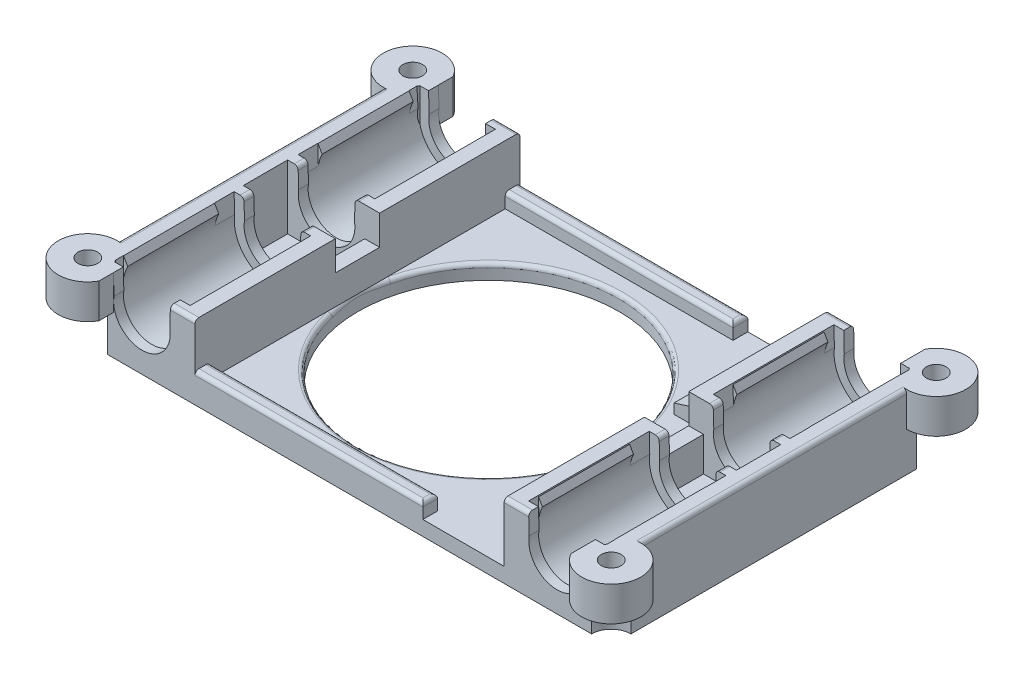
SolidWorks part; units mm, degrees
ref_plane "Front" through (0, 0, 0) normal (0, 0, 1) x (1, 0, 0)
ref_plane "Top" through (0, 0, 0) normal (0, 1, 0) x (1, 0, 0)
ref_plane "Right" through (0, 0, 0) normal (1, 0, 0) x (0, 0, -1)
sketch "Sketch1" plane through (0, 0, 0) normal (0, 1, 0) x (1, 0, 0)
  line L1 (-62.38, 33) -> (62.38, 33)
  line L2 (-62.38, 33) -> (-62.38, -33)
  line L3 (-62.38, -33) -> (62.38, -33)
  line L4 (62.38, 33) -> (62.38, -33)
  dimension "D1" = 124.76
  dimension "D2" = 66
  dimension "6" = 62.38
  dimension "D4" = 33
extrude "Boss-Extrude1" add sketch "Sketch1" along normal blind 20
sketch "Sketch2" plane through (0, 0, 33) normal (0, 0, 1) x (1, 0, 0)
  line L0 (-62.38, 0) -> (62.38, 0) construction
  line L1 (-62.38, 20) -> (-62.38, 0) construction
  line L2 (62.38, 20) -> (62.38, 0) construction
  circle A0 centre (-42.16, 10) radius 7.75
  circle A1 centre (42.16, 10) radius 7.65
  dimension "D2" = 15.5
  dimension "D3" = 15.3
  dimension "D1" = 20.22
  dimension "D4" = 10
  dimension "D5" = 10
  dimension "D6" = 20.22
  dimension "D7" = 84.32
extrude "Cut-Extrude1" cut sketch "Sketch2" against normal through all
sketch "Sketch4" plane through (-62.38, 0, 0) normal (-1, 0, 0) x (0, 0, 1)
  line L0 (-33, 20) -> (33, 20) construction
  line L1 (31, 2) -> (-31, 2)
  line L2 (31, 2) -> (31, 20)
  line L3 (31, 20) -> (-31, 20)
  line L4 (-31, 2) -> (-31, 20)
  line L5 (-33, 0) -> (33, 0) construction
  line L6 (33, 2.35) -> (33, 17.65) construction
  line L9 (-33, 20) -> (-33, 0) construction
  dimension "D1" = 2
  dimension "D2" = 2
  dimension "D3" = 2
extrude "Cut-Extrude2" cut sketch "Sketch4" against normal blind 27.98
sketch "Sketch5" plane through (62.38, 0, 0) normal (1, 0, 0) x (0, 0, -1)
  line L0 (-33, 20) -> (33, 20) construction
  line L1 (-31, 2) -> (31, 2)
  line L2 (-31, 2) -> (-31, 20)
  line L3 (-31, 20) -> (31, 20)
  line L4 (31, 2) -> (31, 20)
  line L5 (-33, 0) -> (33, 0) construction
  line L6 (-33, 20) -> (-33, 0) construction
  line L7 (33, 20) -> (33, 0) construction
  dimension "D1" = 2
  dimension "D2" = 2
  dimension "D3" = 2
extrude "Cut-Extrude3" cut sketch "Sketch5" against normal blind 27.98
sketch "Sketch6" plane through (0, 0, 31) normal (0, 0, -1) x (-1, 0, 0)
  line L0 (34.4, 20) -> (62.38, 20) construction
  line L1 (31.16, 20) -> (53.16, 20)
  line L2 (31.16, 20) -> (31.16, 2)
  line L3 (31.16, 2) -> (53.16, 2)
  line L4 (53.16, 20) -> (53.16, 2)
  line L5 (34.4, 2) -> (62.38, 2) construction
  circle A0 centre (42.16, 10) radius 7.75 construction
  circle A1 centre (42.16, 10) radius 7.75
  dimension "D1" = 22
  dimension "D2" = 11
extrude "Boss-Extrude2" add sketch "Sketch6" along normal blind 24.5
mirror "Mirror1" about plane through (0, 0, 0) normal (0, 0, 1) of "Boss-Extrude2"
mirror "Mirror2" about plane through (0, 0, 0) normal (1, 0, 0) of "Mirror1", "Boss-Extrude2"
sketch "Sketch7" plane through (0, 0, 33) normal (0, 0, 1) x (1, 0, 0)
  line L0 (34.5126, 9.8) -> (34.2459, 20)
  line L2 (-62.38, 20) -> (62.38, 20) construction
  line L3 (34.2459, 20) -> (50.0741, 20)
  line L4 (50.0741, 20) -> (49.8074, 9.8)
  circle A1 centre (42.16, 10) radius 7.65 construction
  arc A2 (34.5126, 9.8) -> (49.8074, 9.8) centre (42.16, 10) ccw
  dimension "D1" = 0.2
  dimension "D2" = 0.2
extrude "Cut-Extrude4" cut sketch "Sketch7" against normal blind 4
mirror "Mirror3" about plane through (0, 0, 0) normal (1, 0, 0) of "Cut-Extrude4"
mirror "Mirror4" about plane through (0, 0, 0) normal (0, 0, 1) of "Mirror3", "Cut-Extrude4"
sketch "Sketch8" plane through (0, 0, -6.5) normal (0, 0, 1) x (1, 0, 0)
  line L0 (49.8074, 9.8) -> (50.0741, 20) construction
  line L1 (34.2459, 20) -> (34.5126, 9.8) construction
  line L2 (49.8074, 9.8) -> (50.0741, 20)
  line L3 (34.2459, 20) -> (34.5126, 9.8)
  line L4 (50.0741, 20) -> (34.2459, 20)
  arc A0 (34.5126, 9.8) -> (49.8074, 9.8) centre (42.16, 10) ccw construction
  arc A1 (34.5126, 9.8) -> (49.8074, 9.8) centre (42.16, 10) ccw
extrude "Cut-Extrude5" cut sketch "Sketch8" against normal blind 4
mirror "Mirror5" about plane through (0, 0, 0) normal (1, 0, 0) of "Cut-Extrude5"
mirror "Mirror6" about plane through (0, 0, 0) normal (0, 0, 1) of "Mirror5", "Cut-Extrude5"
sketch "Sketch10" plane through (0, 0, -29) normal (0, 0, -1) x (-1, 0, 0)
  line L0 (34.3838, 14.7273) -> (35.1748, 13.3571)
  line L1 (49.8398, 11.0405) -> (50.0741, 20) construction
  line L2 (49.9454, 15.0786) -> (50.0741, 20)
  line L3 (50.0741, 20) -> (34.2459, 20)
  line L4 (34.2459, 20) -> (34.3838, 14.7273)
  line L5 (34.2459, 20) -> (34.4802, 11.0405) construction
  line L7 (49.0556, 13.5374) -> (49.9454, 15.0786)
  arc A0 (49.8398, 11.0405) -> (34.4802, 11.0405) centre (42.16, 10) ccw construction
  arc A1 (49.0556, 13.5374) -> (35.1748, 13.3571) centre (42.16, 10) ccw
  point P11 (0, 0)
  dimension "D2" = 151.498
  dimension "D1" = 151.498
extrude "Cut-Extrude6" cut sketch "Sketch10" against normal through all both and the other way through all
mirror "Mirror7" about plane through (0, 0, 0) normal (1, 0, 0) of "Cut-Extrude6"
ref_plane "Plane6" through (0, 10, 0) normal (0, 1, 0) x (1, 0, 0)
sketch "Sketch12" plane through (0, 0, -33) normal (0, 0, -1) x (-1, 0, 0)
  line L2 (48.0748, 20.0523) -> (62.38, 20)
  line L3 (62.38, 20) -> (62.38, 0)
  line L4 (36.2452, 20.0523) -> (36.484, 10.9196)
  line L5 (47.836, 10.9196) -> (48.0748, 20.0523)
  line L6 (36.2452, 20.0523) -> (36.484, 10.9196)
  line L7 (47.836, 10.9196) -> (48.0748, 20.0523)
  line L8 (62.38, 0) -> (30.8026, 0)
  line L9 (-62.38, 0) -> (62.38, 0) construction
  line L10 (30.8026, 0) -> (30.8026, 20)
  line L11 (-34.2459, 20) -> (34.2459, 20) construction
  line L12 (30.8026, 20) -> (36.2452, 20.0523)
  arc A2 (36.484, 10.9196) -> (47.836, 10.9196) centre (42.16, 10) ccw
  arc A3 (36.484, 10.9196) -> (47.836, 10.9196) centre (42.16, 10) ccw
  dimension "D1" = 2
extrude "Boss-Extrude3" add sketch "Sketch12" against normal blind 2
mirror "Mirror10" about plane through (0, 0, 0) normal (1, 0, 0) of "Boss-Extrude3"
mirror "Mirror11" about plane through (0, 0, 0) normal (0, 0, 1) of "Boss-Extrude3", "Mirror10"
sketch "Sketch13" plane through (0, 0, 6.5) normal (0, 0, -1) x (-1, 0, 0)
  line L0 (48.0748, 20.0523) -> (47.836, 10.9196) construction
  line L1 (36.484, 10.9196) -> (36.2452, 20.0523) construction
  line L2 (48.0748, 20.0523) -> (47.836, 10.9196)
  line L3 (36.484, 10.9196) -> (36.2452, 20.0523)
  line L4 (50.0741, 20) -> (48.0748, 20.0523)
  line L5 (50.0741, 20) -> (53.16, 20)
  line L6 (53.16, 20) -> (53.16, 2)
  line L7 (34.4, 2) -> (53.16, 2) construction
  line L8 (53.16, 2) -> (28.78, 2)
  line L9 (28.78, 2) -> (28.78, 20)
  line L11 (28.78, 20) -> (36.2452, 20.0523)
  arc A0 (36.484, 10.9196) -> (47.836, 10.9196) centre (42.16, 10) ccw construction
  arc A1 (36.484, 10.9196) -> (47.836, 10.9196) centre (42.16, 10) ccw
  dimension "D1" = 24.38
extrude "Boss-Extrude4" add sketch "Sketch13" along normal blind 2
mirror "Mirror12" about plane through (0, 0, 0) normal (1, 0, 0) of "Boss-Extrude4"
mirror "Mirror13" about plane through (0, 0, 0) normal (0, 0, 1) of "Mirror12", "Boss-Extrude4"
sketch "Sketch14" plane through (0, 0, 0) normal (0, -1, 0) x (1, 0, 0)
  line L0 (53.16, 4.5) -> (53.16, 31) construction
  line L1 (53.16, -33) -> (53.16, 33)
  line L2 (-62.38, 33) -> (62.38, 33) construction
  line L3 (62.38, 33) -> (62.38, -33) construction
  line L4 (62.38, 33) -> (62.38, -33)
  line L5 (53.16, 33) -> (62.38, 33)
  line L6 (53.16, -33) -> (62.38, -33)
extrude "Cut-Extrude9" cut sketch "Sketch14" against normal through all
mirror "Mirror15" about plane through (0, 0, 0) normal (1, 0, 0) of "Cut-Extrude9"
sketch "Sketch15" plane through (0, 20, 0) normal (0, 1, 0) x (1, 0, 0)
  line L0 (31.4, -33) -> (31.4, 33)
  line L1 (-30.8026, -33) -> (30.8026, -33) construction
  line L2 (30.8026, 33) -> (-30.8026, 33) construction
  line L3 (53.16, -4.5) -> (53.16, 4.5) construction
  line L4 (-31.38, -33) -> (-31.38, 33)
  line L5 (-31.38, 33) -> (31.4, 33)
  line L6 (31.4, -33) -> (-31.38, -33)
  dimension "D1" = 21.76
  dimension "D2" = 62.78
extrude "Cut-Extrude10" cut sketch "Sketch15" against normal blind 17
sketch "Sketch16" plane through (0, 2, 0) normal (0, 1, 0) x (1, 0, 0)
  line L2 (-53.16, 4.5) -> (-53.16, -4.5)
  line L3 (-53.16, -4.5) -> (-50.0741, -4.5)
  line L4 (-34.4, -4.5) -> (-53.16, -4.5) construction
  line L5 (-53.16, 4.5) -> (-50.0741, 4.5)
  line L6 (-50.0741, 6.5) -> (-50.0741, 31) construction
  line L7 (-50.0741, -4.5) -> (-50.0741, 4.5)
extrude "Boss-Extrude6" add sketch "Sketch16" along normal up to vertex (18 mm away)
mirror "Mirror16" about plane through (0, 0, 0) normal (1, 0, 0) of "Boss-Extrude6"
sketch "Sketch17" plane through (53.16, 0, 0) normal (1, 0, 0) x (0, 0, -1)
  line L0 (20.9433, 20) -> (10.8, 11)
  line L1 (10.8, 11) -> (-9.9399, 11)
  line L2 (-9.9399, 11) -> (-20.9009, 20)
  line L3 (31, 20) -> (-31, 20) construction
  line L4 (50, 10) -> (-50, 10) construction
  line L5 (20.9433, 20) -> (-20.9009, 20)
  dimension "D1" = 1
extrude "Cut-Extrude11" [suppressed] cut sketch "Sketch17" against normal blind 16
mirror "Mirror17" [suppressed] about plane through (0, 0, 0) normal (1, 0, 0)
sketch "Sketch18" plane through (0, 0, 0) normal (0, -1, 0) x (1, 0, 0)
  line L1 (22.4, 8) -> (22.4, 23)
  line L2 (31.4, 33) -> (31.4, -33) construction
  line L3 (31.4, 23) -> (31.4, 8)
  line L5 (31.4, 23) -> (22.4, 23)
  line L6 (50, 0) -> (-50, 0) construction
  line L7 (22.4, 8) -> (31.4, 8)
  dimension "D1" = 23
  dimension "D2" = 15
  dimension "D3" = 9
extrude "Cut-Extrude12" [suppressed] cut sketch "Sketch18" against normal blind 25
mirror "Mirror18" [suppressed] about plane through (0, 0, 0) normal (0, 0, 1)
sketch "Sketch19" plane through (31.4, 0, 0) normal (-1, 0, 0) x (0, 0, 1)
  line L1 (-21.5, 6.5) -> (-9.5, 6.5)
  line L2 (-21.5, 6.5) -> (-21.5, 4.5)
  line L3 (-21.5, 4.5) -> (-9.5, 4.5)
  line L4 (-9.5, 6.5) -> (-9.5, 4.5)
  line L7 (33, 3) -> (-33, 3) construction
  line L8 (-33, 3) -> (-33, 20) construction
  dimension "D1" = 11.5
  dimension "D2" = 2
  dimension "D3" = 12
  dimension "D4" = 1.5
extrude "Boss-Extrude7" add sketch "Sketch19" along normal blind 8
mirror "Mirror19" about plane through (0, 0, 0) normal (0, 0, 1) of "Boss-Extrude7"
sketch "Sketch21" plane through (0, 20, 0) normal (0, 1, 0) x (1, 0, 0)
  line L2 (-34.4, 4.5) -> (-34.4, -4.5) construction
  line L6 (-30.8026, 33) -> (-31.38, 33) construction
  circle A0 centre (-4.77, 0) radius 26.5
  dimension "D1" = 53
  dimension "D2" = 29.63
  dimension "D3" = 33
extrude "Cut-Extrude13" cut sketch "Sketch21" against normal through all
sketch "Sketch23" plane through (0, 0, 33) normal (0, 0, 1) x (1, 0, 0)
  line L0 (-53.16, 20.5) -> (53.16, 20.5)
  line L2 (-53.16, 0) -> (53.16, 0) construction
  line L3 (53.16, 15) -> (-53.16, 15)
  line L4 (53.16, 20.0337) -> (53.16, 0) construction
  line L6 (-53.16, 20.0337) -> (-53.16, 0) construction
  line L7 (-53.16, 15) -> (-53.16, 20.5)
  line L8 (53.16, 15) -> (53.16, 20.5)
  dimension "D1" = 15
  dimension "D2" = 5.5
extrude "Cut-Extrude18" cut sketch "Sketch23" against normal through all
sketch "Sketch27" plane through (-31.38, 0, 0) normal (1, 0, 0) x (0, 0, -1)
  line L2 (-4.5, 15) -> (-4.5, 8.98)
  line L3 (4.5, 8.98) -> (4.5, 15)
  line L5 (4.5, 15) -> (-4.5, 15)
  line L8 (4.5, 8.98) -> (-4.5, 8.98)
  line L10 (33, 15) -> (-33, 15) construction
  line L11 (-4.5, 14.6992) -> (-4.5, 2) construction
  line L12 (4.5, 2) -> (4.5, 14.6992) construction
  dimension "D1" = 6.02
extrude "Cut-Extrude20" cut sketch "Sketch27" against normal blind 6
sketch "Sketch28" plane through (34.4, 0, 0) normal (1, 0, 0) x (0, 0, -1)
  line L0 (4.5, 2) -> (4.5, 14.6992) construction
  line L1 (-4.5, 15) -> (4.5, 15)
  line L2 (-4.5, 15) -> (-4.5, 8.98)
  line L3 (-4.5, 8.98) -> (4.5, 8.98)
  line L4 (4.5, 15) -> (4.5, 8.98)
  line L5 (-4.5, 14.6992) -> (-4.5, 2) construction
  dimension "D1" = 6.02
extrude "Cut-Extrude21" cut sketch "Sketch28" against normal blind 6
sketch "Sketch29" plane through (0, 3, 0) normal (0, 1, 0) x (1, 0, 0)
  line L0 (-31.38, 33) -> (-31.38, -33) construction
  line L2 (31.4, 33) -> (-31.38, 33) construction
  line L3 (14.8966, 33) -> (-31.38, 33)
  line L5 (-31.38, -33) -> (31.4, -33) construction
  line L6 (-31.38, -33) -> (14.8966, -33)
  line L7 (-31.38, -30) -> (-31.38, -33)
  line L8 (-31.38, 33) -> (-31.38, 30)
  line L26 (14.8966, 30) -> (14.8966, 33)
  line L29 (14.8966, -33) -> (14.8966, -30)
  line L33 (-31.38, -30) -> (14.8966, -30)
  line L35 (14.8966, 30) -> (-31.38, 30)
  point P11 (18.4, 23)
  point P12 (18.4, 33)
  point P36 (19.4, 5)
  point P37 (27.38, 5)
  point P38 (24.38, 8)
  point P39 (21.9, -5)
  dimension "D1" = 46.2766
  dimension "D2" = 3
  dimension "D3" = 3
sketch "Sketch30" plane through (0, 0, 0) normal (0, -1, 0) x (1, 0, 0)
  line L1 (-53.16, 33) -> (53.16, 33) construction
  line L2 (-53.16, 33) -> (-53.16, -33) construction
  line L3 (-53.16, 33) -> (-49.16, 33)
  line L4 (-53.16, 33) -> (-53.16, 29)
  arc A0 (-49.16, 33) -> (-53.16, 29) centre (-53.16, 33) cw
  dimension "D1" = 4
extrude "Boss-Extrude11" add sketch "Sketch29" along normal blind 3
extrude "Cut-Extrude24" cut sketch "Sketch30" against normal through all
mirror "Mirror20" about plane through (0, 0, 0) normal (0, 0, 1) of "Cut-Extrude24"
mirror "Mirror21" about plane through (0, 0, 0) normal (1, 0, 0) of "Mirror20", "Cut-Extrude24"
ref_plane "Plane7" through (31.4, 6.5, 9.5) normal (0, 0, 1) x (1, 0, 0)
sketch "Sketch32" plane through (31.4, 6.5, 9.5) normal (0, 0, 1) x (1, 0, 0)
  line L0 (-8, 0) -> (0, 2.48)
  line L1 (-8, 0) -> (0, 0) construction
  line L2 (0, 0) -> (0, 3.7007) construction
rib "Rib1" sketch "Sketch32" sketch "Sketch32" thickness 12 parameters "D1"=12
mirror "Mirror22" about plane through (0, 0, 0) normal (0, 0, 1) of "Rib1"
sketch "Sketch36" plane through (31.4, 0, 0) normal (-1, 0, 0) x (0, 0, 1)
  line L0 (15.015, 4.1169) -> (14.9192, 4.5)
  line L1 (15.5, 4.5) -> (15.5, -6.0947) construction
  line L2 (21.5, 4.5) -> (9.5, 4.5) construction
  line L3 (15.985, 4.1169) -> (16.0808, 4.5)
  line L4 (14.9192, 4.5) -> (16.0808, 4.5)
  arc A0 (15.015, 4.1169) -> (15.985, 4.1169) centre (15.5, 4.2382) ccw
  dimension "D1" = 1.1617
  dimension "D2" = 28.082
  dimension "D3" = 0.3831
extrude "Boss-Extrude8" add sketch "Sketch36" along normal up to surface (8 mm away) up to face at (23.4, 5.5, 15.5)
pattern_linear "LPattern1" count 3 spacing 2 along (0, 0, 1) count 3 spacing 2 along (0, 0, -1) of "Boss-Extrude8"
mirror "Mirror23" about plane through (0, 0, 0) normal (0, 0, 1) of "LPattern1", "Boss-Extrude8"
sketch "Sketch40" plane through (0, 2, 0) normal (0, 1, 0) x (1, 0, 0)
  line L0 (0, 0) -> (19.5479, 0) construction
  line L2 (50.0741, -4.5) -> (50.0741, 4.5) construction
  line L3 (-50.0741, -4.5) -> (-50.0741, 4.5) construction
  circle A0 centre (42.2391, 0) radius 2.375
  circle A1 centre (-42.2391, 0) radius 2.375
  dimension "D1" = 4.75
  dimension "D2" = 7.835
  dimension "D3" = 4.75
  dimension "D4" = 7.835
extrude "Cut-Extrude27" cut sketch "Sketch40" against normal up to next
sketch "Sketch37" plane through (0, 0, 0) normal (0, -1, 0) x (1, 0, 0)
  line L0 (-49.16, 33) -> (49.16, 33) construction
  line L1 (11.16, 33) -> (13.23, 33)
  line L2 (11.16, 33) -> (11.16, 30.93)
  line L3 (11.16, 30.93) -> (13.23, 30.93)
  line L4 (13.23, 33) -> (13.23, 30.93)
  line L5 (49.16, -33) -> (-49.16, -33) construction
  line L6 (-22.77, 33) -> (-24.84, 33)
  line L7 (-22.77, 33) -> (-22.77, 30.93)
  line L8 (-22.77, 30.93) -> (-24.84, 30.93)
  line L9 (-24.84, 33) -> (-24.84, 30.93)
  line L10 (11.16, -33) -> (13.23, -33)
  line L11 (11.16, -33) -> (11.16, -30.93)
  line L12 (11.16, -30.93) -> (13.23, -30.93)
  line L13 (13.23, -33) -> (13.23, -30.93)
  line L14 (53.16, 29) -> (53.16, -29) construction
  line L15 (-22.77, -33) -> (-24.84, -33)
  line L16 (-22.77, -33) -> (-22.77, -30.93)
  line L17 (-22.77, -30.93) -> (-24.84, -30.93)
  line L18 (-24.84, -33) -> (-24.84, -30.93)
  circle A0 centre (-4.77, 0) radius 26.5 construction
  dimension "D1" = 42
  dimension "D2" = 36
  dimension "D3" = 18
  dimension "D4" = 2.07
extrude "Boss-Extrude9" [suppressed] add sketch "Sketch37" along normal blind 3
sketch "Sketch39" plane through (0, 0, 0) normal (0, -1, 0) x (1, 0, 0)
  line L0 (-53.16, 29) -> (-53.16, -29) construction
  line L1 (49.16, -33) -> (-49.16, -33) construction
  line L2 (-49.16, 33) -> (49.16, 33) construction
  circle A0 centre (21.1, 26) radius 2.175
  circle A1 centre (-18.9, 26) radius 2.175
  circle A2 centre (21.1, -26) radius 2.175
  circle A3 centre (-18.9, -26) radius 2.175
  dimension "D1" = 7
  dimension "D3" = 40
  dimension "D5" = 4.35
  dimension "D2" = 7
  dimension "D4" = 34.26
extrude "Cut-Extrude26" [suppressed] cut sketch "Sketch39" against normal up to next
sketch "Sketch38" plane through (0, 0, 0) normal (0, -1, 0) x (1, 0, 0)
  line L0 (53.16, 29) -> (53.16, -29) construction
  line L1 (49.96, 10.8) -> (45.36, 10.8)
  line L2 (49.96, 10.8) -> (49.96, 5.7)
  line L3 (49.96, 5.7) -> (45.36, 5.7)
  line L4 (45.36, 10.8) -> (45.36, 5.7)
  line L6 (-43.36, 10.8) -> (-46.96, 10.8)
  line L7 (-43.36, 10.8) -> (-43.36, -10.8)
  line L8 (-43.36, -10.8) -> (-46.96, -10.8)
  line L9 (-46.96, 10.8) -> (-46.96, -10.8)
  line L10 (-53.16, 29) -> (-53.16, -29) construction
  circle A0 centre (-4.77, 0) radius 26.5 construction
  dimension "D3" = 10.8
  dimension "D7" = 10.8
  dimension "D1" = 5.1
  dimension "D2" = 4.6
  dimension "D4" = 3.2
  dimension "D5" = 21.6
  dimension "D6" = 3.6
  dimension "D8" = 9.8
extrude "Boss-Extrude10" [suppressed] add sketch "Sketch38" along normal blind 2.7
sketch "Sketch44" plane through (0, 15, 0) normal (0, 1, 0) x (1, 0, 0)
  line L0 (-53.16, 29) -> (-53.16, -29) construction
  line L1 (-53.16, -33) -> (-53.16, -29)
  line L2 (-49.16, -33) -> (-53.16, -33)
  line L3 (-47.9427, -33) -> (-47.9427, -35.9631)
  line L4 (47.16, -33) -> (53.16, -33)
  line L5 (53.16, -33) -> (53.16, -27)
  line L6 (-49.16, -33) -> (-47.16, -33)
  line L7 (47.9427, -33) -> (47.9427, -35.9631)
  line L8 (-53.16, -29) -> (-53.16, -27)
  line L9 (47.16, 33) -> (53.16, 33)
  line L10 (53.16, 33) -> (53.16, 27)
  line L11 (47.9427, 33) -> (47.9427, 35.9631)
  line L13 (-53.16, 27) -> (-53.16, 33)
  line L14 (-53.16, 33) -> (-47.16, 33)
  line L16 (-47.9427, 33) -> (-47.9427, 35.9631)
  circle A0 centre (-53.16, -33) radius 6
  circle A1 centre (-53.16, 33) radius 6
  circle A2 centre (53.16, 33) radius 6
  circle A3 centre (53.16, -33) radius 6
  arc A4 (-49.16, -33) -> (-53.16, -29) centre (-53.16, -33) ccw
  arc A6 (-53.16, 29) -> (-49.16, 33) centre (-53.16, 33) ccw
  arc A7 (53.16, 29) -> (49.16, 33) centre (53.16, 33) cw
  arc A8 (53.16, -29) -> (49.16, -33) centre (53.16, -33) ccw
  circle A9 centre (53.16, 33) radius 2
  circle A10 centre (53.16, -33) radius 2
  circle A11 centre (-53.16, -33) radius 2
  circle A12 centre (-53.16, 33) radius 2
extrude "Boss-Extrude14" add sketch "Sketch44" against normal blind 7
fillet "Fillet1" radius 0.8 6 edges at (33.8887, 15, 33) (-53.16, 15, 0) (53.16, 15, 0) (-33.8787, 15, 33) (33.8887, 15, -33) (-33.8787, 15, -33)
fillet "Fillet2" radius 0.8 15 edges at (-8.2417, 6, 30) (-8.2417, 6, 33) (14.8966, 6, 31.5) (-8.2417, 6, -30) (14.8966, 6, -31.5) (-8.2417, 6, -33) (-4.77, 3, -26.5) (36.3773, 15, -5.5) (-36.3773, 15, 5.5) (36.3773, 15, 5.5) (47.9427, 15, 5.5) (-47.9427, 15, -5.5) (-36.3773, 15, -5.5) (47.9427, 15, -5.5) (-47.9427, 15, 5.5)
